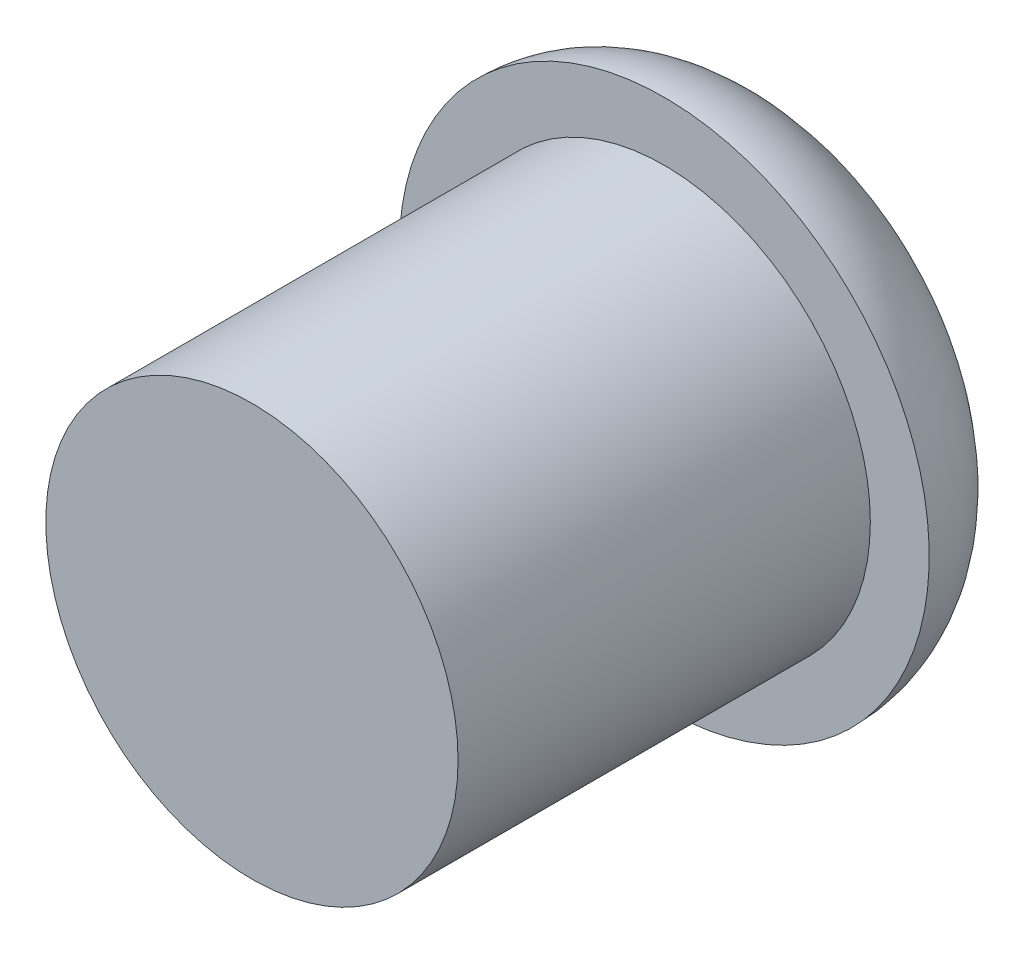
SolidWorks part; units mm, degrees
material "AISI 304"
ref_plane "Alzado" through (0, 0, 0) normal (0, 0, 1) x (1, 0, 0)
ref_plane "Planta" through (0, 0, 0) normal (0, 1, 0) x (1, 0, 0)
ref_plane "Vista lateral" through (0, 0, 0) normal (1, 0, 0) x (0, 0, -1)
sketch "Croquis1" plane through (0, 0, 0) normal (0, 0, 1) x (1, 0, 0)
  circle A0 centre (0, 0) radius 3.5
  dimension "D1" = 7
extrude "Saliente-Extruir1" add sketch "Croquis1" along normal blind 7
sketch "Croquis2" plane through (0, 0, 0) normal (0, 0, -1) x (-1, 0, 0)
  circle A0 centre (0, 0) radius 4.5
  dimension "D1" = 9
extrude "Saliente-Extruir2" add sketch "Croquis2" along normal blind 2
fillet "Redondeo1" radius 2 1 edges at (-4.5, 0, -2)
